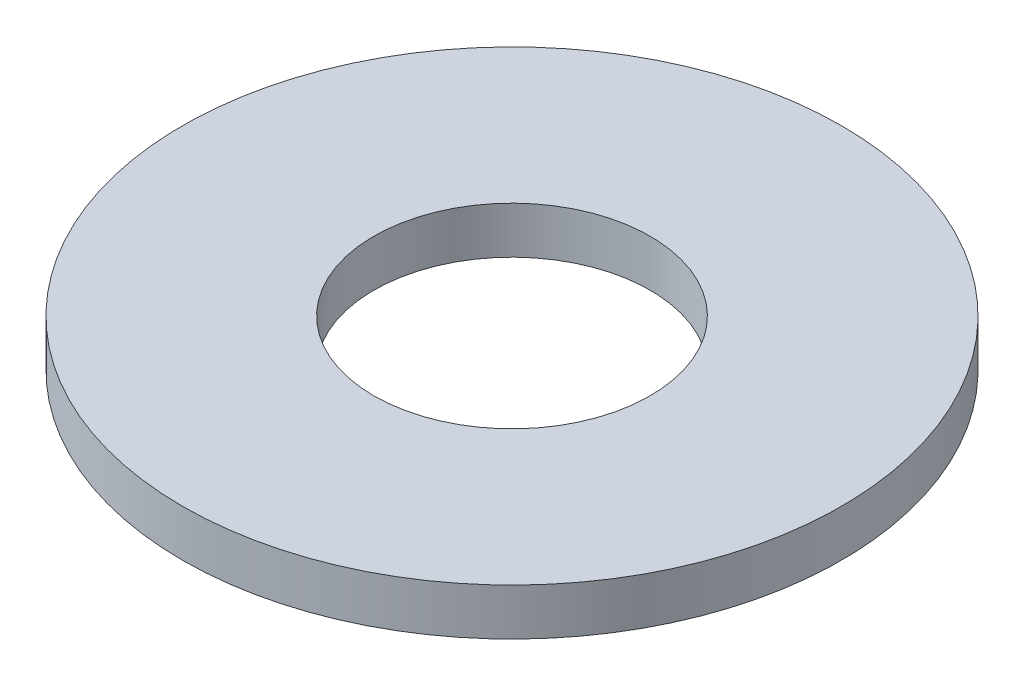
SolidWorks part; units mm, degrees
ref_plane "Front Plane" through (0, 0, 0) normal (0, 0, 1) x (1, 0, 0)
ref_plane "Top Plane" through (0, 0, 0) normal (0, 1, 0) x (1, 0, 0)
ref_plane "Right Plane" through (0, 0, 0) normal (1, 0, 0) x (0, 0, -1)
sketch "Sketch1" plane through (0, 0, 0) normal (0, 1, 0) x (1, 0, 0)
  circle A0 centre (0, 0) radius 77.5
  dimension "FLANGE_OD" = 155
extrude "Boss-Extrude1" add sketch "Sketch1" along normal blind 11
sketch "Sketch2" plane through (0, 0, 0) normal (0, 1, 0) x (1, 0, 0)
  circle A0 centre (0, 0) radius 32.5
  dimension "BORE_D" = 65
extrude "Cut-Extrude1" cut sketch "Sketch2" along normal through all
sketch "Sketch3" plane through (0, 11, 0) normal (0, 1, 0) x (1, 0, 0)
  circle A0 centre (0, 0) radius 23.7687 construction
  circle A1 centre (-23.7687, 0) radius 4.2403
  dimension "BOLT_D" = 8.4806
  dimension "BOLT_PCD" = 47.5373
extrude "Cut-Extrude2" cut sketch "Sketch3" against normal blind 7.3383 rebuild error yes
pattern_circular "CirPattern1" count 6 over 360 rebuild error yes
